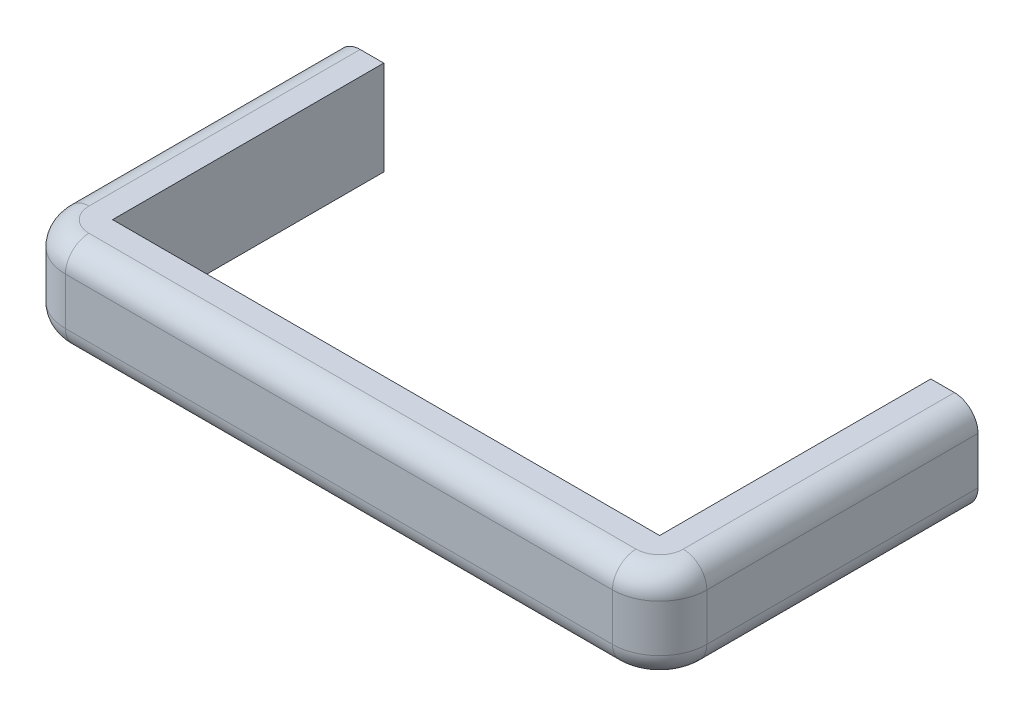
SolidWorks part; units mm, degrees
material "Polyurethane Foam Flexible"
ref_plane "Front Plane" through (0, 0, 0) normal (0, 0, 1) x (1, 0, 0)
ref_plane "Top Plane" through (0, 0, 0) normal (0, 1, 0) x (1, 0, 0)
ref_plane "Right Plane" through (0, 0, 0) normal (1, 0, 0) x (0, 0, -1)
sketch "Sketch1" plane through (0, 0, 0) normal (1, 0, 0) x (0, 0, -1)
  line L0 (-31.75, 0) -> (-31.75, -63.5)
  line L1 (31.75, 0) -> (31.75, -95.25)
  line L2 (0, -95.25) -> (31.75, -95.25)
  line L3 (31.75, 0) -> (31.75, 31.75)
  line L4 (0, 31.75) -> (31.75, 31.75)
  arc A0 (0, 31.75) -> (-31.75, 0) centre (0, 0) ccw
  arc A1 (-31.75, -63.5) -> (0, -95.25) centre (0, -63.5) ccw
  arc A2 (31.75, 0) -> (0, 31.75) centre (0, 0) ccw construction
  arc A3 (0, -31.75) -> (31.75, 0) centre (0, 0) ccw construction
  arc A4 (31.75, -63.5) -> (0, -31.75) centre (0, -63.5) ccw construction
  arc A5 (-31.75, 0) -> (0, -31.75) centre (0, 0) ccw construction
  arc A6 (0, -31.75) -> (-31.75, -63.5) centre (0, -63.5) ccw construction
  arc A7 (0, -95.25) -> (31.75, -63.5) centre (0, -63.5) ccw construction
  dimension "D1" = 63.5
  dimension "D2" = 63.5
extrude "Boss-Extrude1" add sketch "Sketch1" along normal blind 736.6 contours L0 A1 L2 L1 L3 L4 A0 region at (0, -31.75, -1.3979)
sketch "Sketch8" plane through (736.6, 0, 0) normal (1, 0, 0) x (0, 0, -1)
  line L8 (-31.75, 0) -> (-31.75, -63.5)
  line L9 (0, -95.25) -> (31.75, -95.25)
  line L10 (31.75, -95.25) -> (31.75, 31.75)
  line L11 (31.75, 31.75) -> (0, 31.75)
  line L12 (-31.75, 0) -> (-31.75, -63.5)
  line L13 (0, -95.25) -> (31.75, -95.25)
  line L14 (31.75, -95.25) -> (31.75, 31.75)
  line L15 (31.75, 31.75) -> (0, 31.75)
  arc A4 (-31.75, -63.5) -> (0, -95.25) centre (0, -63.5) ccw
  arc A5 (0, 31.75) -> (-31.75, 0) centre (0, 0) ccw
  arc A6 (-31.75, -63.5) -> (0, -95.25) centre (0, -63.5) ccw
  arc A7 (0, 31.75) -> (-31.75, 0) centre (0, 0) ccw
  dimension "D1" = 0
revolve "Revolve13" add sketch "Sketch8" angle 90 about L14
sketch "Sketch15" plane through (0, 0, -31.75) normal (-1, 0, 0) x (0, 0, 1)
  line L14 (63.5, -63.5) -> (63.5, 0)
  line L20 (31.75, 31.75) -> (0, 31.75)
  line L21 (0, 31.75) -> (0, -95.25)
  line L22 (0, -95.25) -> (31.75, -95.25)
  line L23 (63.5, -63.5) -> (63.5, 0)
  line L24 (31.75, 31.75) -> (0, 31.75)
  line L25 (0, 31.75) -> (0, -95.25)
  line L26 (0, -95.25) -> (31.75, -95.25)
  arc A8 (63.5, 0) -> (31.75, 31.75) centre (31.75, 0) ccw
  arc A9 (31.75, -95.25) -> (63.5, -63.5) centre (31.75, -63.5) ccw
  arc A10 (63.5, 0) -> (31.75, 31.75) centre (31.75, 0) ccw
  arc A11 (31.75, -95.25) -> (63.5, -63.5) centre (31.75, -63.5) ccw
  dimension "D1" = 0
revolve "Revolve12" add sketch "Sketch15" angle 90 about L25 region at (0, -31.75, -1.3979)
sketch "Sketch7" plane through (0, 0, -31.75) normal (0, 0, -1) x (-1, 0, 0)
  line L6 (-800.1, 0) -> (-800.1, -63.5)
  line L7 (-768.35, -95.25) -> (-736.6, -95.25)
  line L8 (-736.6, -95.25) -> (-736.6, 31.75)
  line L9 (-736.6, 31.75) -> (-768.35, 31.75)
  line L10 (-800.1, 0) -> (-800.1, -63.5)
  line L11 (-768.35, -95.25) -> (-736.6, -95.25)
  line L12 (-736.6, -95.25) -> (-736.6, 31.75)
  line L13 (-736.6, 31.75) -> (-768.35, 31.75)
  arc A4 (-768.35, 31.75) -> (-800.1, 0) centre (-768.35, 0) ccw
  arc A5 (-800.1, -63.5) -> (-768.35, -95.25) centre (-768.35, -63.5) ccw
  arc A6 (-768.35, 31.75) -> (-800.1, 0) centre (-768.35, 0) ccw
  arc A7 (-800.1, -63.5) -> (-768.35, -95.25) centre (-768.35, -63.5) ccw
  line M4 (-736.6, 31.75) -> (-736.6, -95.25)
  dimension "D1" = 0
extrude "Boss-Extrude3" add sketch "Sketch7" along normal blind 736.6 contours M4 | M4 region at (766.9521, -31.75, -31.75)
sketch "Sketch12" plane through (1454.15, 0, -768.35) normal (0, 0, -1) x (-1, 0, 0)
  line L13 (654.05, 0) -> (654.05, -63.5)
  line L20 (685.8, -95.25) -> (717.55, -95.25)
  line L21 (717.55, -95.25) -> (717.55, 31.75)
  line L22 (717.55, 31.75) -> (685.8, 31.75)
  line L23 (654.05, 0) -> (654.05, -63.5)
  line L24 (685.8, -95.25) -> (717.55, -95.25)
  line L25 (717.55, -95.25) -> (717.55, 31.75)
  line L26 (717.55, 31.75) -> (685.8, 31.75)
  arc A8 (654.05, -63.5) -> (685.8, -95.25) centre (685.8, -63.5) ccw
  arc A9 (685.8, 31.75) -> (654.05, 0) centre (685.8, 0) ccw
  arc A10 (654.05, -63.5) -> (685.8, -95.25) centre (685.8, -63.5) ccw
  arc A11 (685.8, 31.75) -> (654.05, 0) centre (685.8, 0) ccw
  dimension "D1" = 0
revolve "Revolve2" add sketch "Sketch12" angle 90 about L25 region at (766.9521, -31.75, -768.35)
sketch "Sketch9" plane through (0, 0, -31.75) normal (0, 0, -1) x (-1, 0, 0)
  line L0 (31.75, 31.75) -> (0, 31.75)
  line L1 (31.75, -95.25) -> (0, -95.25)
  line L2 (0, 31.75) -> (0, -95.25)
  line L3 (63.5, 0) -> (63.5, -63.5)
  line L4 (-736.6, 31.75) -> (0, 31.75) construction
  line L5 (0, -95.25) -> (0, 31.75) construction
  circle A0 centre (31.75, 0) radius 31.75
  circle A1 centre (31.75, -63.5) radius 31.75
  line M5 (0, -95.25) -> (0, 31.75)
  dimension "D1" = 63.5
  dimension "D2" = 0
  dimension "D3" = 0
extrude "Boss-Extrude4" add sketch "Sketch9" along normal blind 736.6 contours A0 L0 L2 | A0 | A1 A0 L2 | A1 L3 A0 | A1 | A1 L1 M5 region at (-7.0919, 24.6581, -31.75) region at (-31.75, 0, -31.75) region at (-56.4081, -31.75, -31.75) region at (-7.0919, -31.75, -31.75) region at (-31.75, -63.5, -31.75) region at (-7.0919, -88.1581, -31.75)
sketch "Sketch14" plane through (0, 0, -768.35) normal (0, 0, -1) x (-1, 0, 0)
  line L12 (0, 31.75) -> (0, -95.25)
  line L13 (0, -95.25) -> (31.75, -95.25)
  line L14 (63.5, -63.5) -> (63.5, 0)
  line L15 (31.75, 31.75) -> (0, 31.75)
  line L16 (0, 31.75) -> (0, -95.25)
  line L17 (0, -95.25) -> (31.75, -95.25)
  line L18 (63.5, -63.5) -> (63.5, 0)
  line L19 (31.75, 31.75) -> (0, 31.75)
  arc A4 (31.75, -95.25) -> (63.5, -63.5) centre (31.75, -63.5) ccw
  arc A5 (63.5, 0) -> (31.75, 31.75) centre (31.75, 0) ccw
  arc A6 (31.75, -95.25) -> (63.5, -63.5) centre (31.75, -63.5) ccw
  arc A7 (63.5, 0) -> (31.75, 31.75) centre (31.75, 0) ccw
  dimension "D1" = 0
revolve "Revolve10" add sketch "Sketch14" angle 90 about L16 region at (-30.3521, -31.75, -768.35)
sketch "Sketch10" plane through (0, 0, 0) normal (1, 0, 0) x (0, 0, -1)
  line L4 (800.1, 31.75) -> (768.35, 31.75)
  line L7 (768.35, 31.75) -> (768.35, -95.25)
  line L8 (768.35, -95.25) -> (800.1, -95.25)
  line L9 (831.85, -63.5) -> (831.85, 0)
  line L10 (800.1, 31.75) -> (768.35, 31.75)
  line L12 (768.35, -95.25) -> (800.1, -95.25)
  line L13 (831.85, -63.5) -> (831.85, 0)
  line L15 (768.35, 31.75) -> (768.35, -95.25)
  arc A4 (800.1, -95.25) -> (831.85, -63.5) centre (800.1, -63.5) ccw
  arc A5 (831.85, 0) -> (800.1, 31.75) centre (800.1, 0) ccw
  arc A6 (800.1, -95.25) -> (831.85, -63.5) centre (800.1, -63.5) ccw
  arc A7 (831.85, 0) -> (800.1, 31.75) centre (800.1, 0) ccw
  line M7 (768.35, -95.25) -> (768.35, 31.75)
  dimension "D1" = 0
extrude "Boss-Extrude5" add sketch "Sketch10" along normal blind 736.6 separate body contours M7 | M7 region at (0, -31.75, -798.7021)
combine bodies "Combine1" operation type add bodies to combine 105 115 108
sketch "Sketch16" plane through (800.1, 0, 0) normal (1, 0, 0) x (0, 0, -1)
  line L1 (831.85, 31.75) -> (396.875, 31.75)
  line L2 (831.85, 31.75) -> (831.85, -95.25)
  line L3 (831.85, -95.25) -> (396.875, -95.25)
  line L4 (396.875, 31.75) -> (396.875, -95.25)
  line L6 (831.85, -63.5) -> (831.85, 0) construction
  line L7 (768.35, 31.75) -> (31.75, 31.75) construction
  line L8 (768.35, -95.25) -> (31.75, -95.25) construction
  line L9 (768.35, 0) -> (31.75, 0) construction
  point P6 (400.05, 0)
  dimension "D1" = 3.175
extrude "Cut-Extrude1" cut sketch "Sketch16" against normal through all
equation "\"foamlength\"=29"
equation "\"D1@Boss-Extrude1\"=\"foamlength\""
equation "\"D1@Boss-Extrude3\"=\"foamlength\""
equation "\"D1@Boss-Extrude4\"=\"foamlength\""
equation "\"D1@Boss-Extrude5\"=\"foamlength\""
